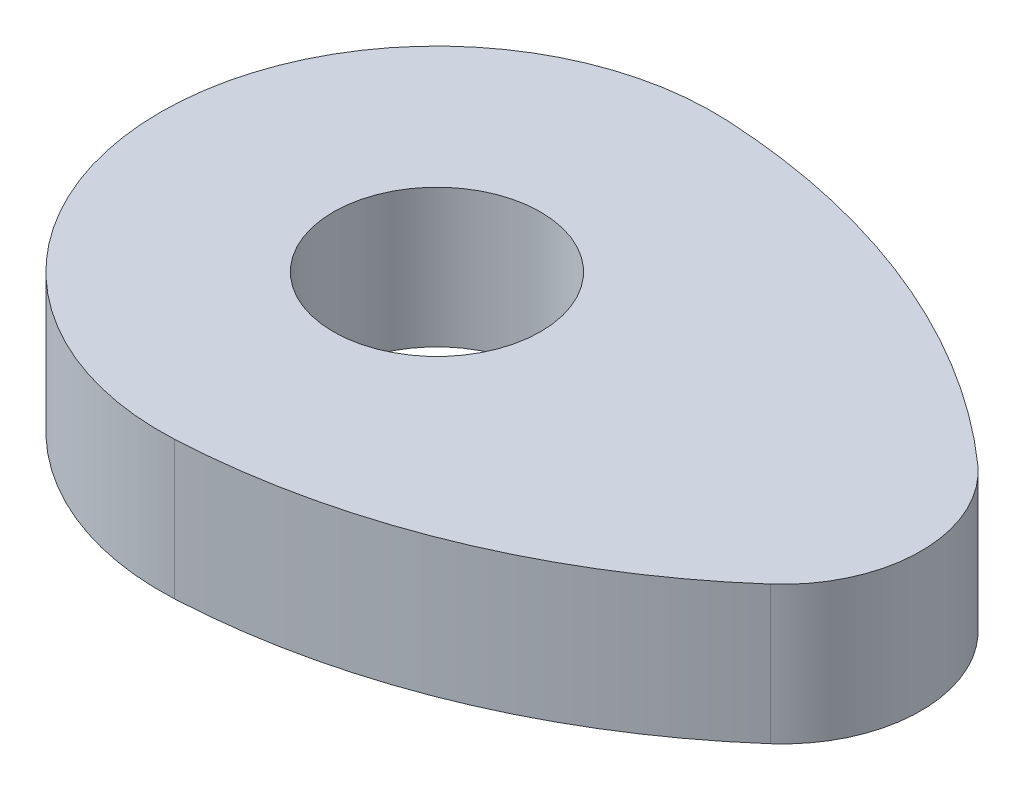
SolidWorks part; units mm, degrees
ref_plane "Front Plane" through (0, 0, 0) normal (0, 0, 1) x (1, 0, 0)
ref_plane "Top Plane" through (0, 0, 0) normal (0, 1, 0) x (1, 0, 0)
ref_plane "Right Plane" through (0, 0, 0) normal (1, 0, 0) x (0, 0, -1)
sketch "Sketch1" plane through (0, 0, 0) normal (0, 1, 0) x (1, 0, 0)
  arc A0 (1, 19.975) -> (1, -19.975) centre (0, 0) ccw
  arc A1 (31.625, -7.4906) -> (31.625, 7.4906) centre (25, 0) ccw
  arc A2 (1, 19.975) -> (31.625, 7.4906) centre (-1.5, -29.9625) cw
  arc A3 (1, -19.975) -> (31.625, -7.4906) centre (-1.5, 29.9625) ccw
  circle A4 centre (0, 0) radius 7.5
  dimension "D1" = 40
  dimension "D2" = 20
  dimension "D4" = 50
  dimension "D5" = 50
  dimension "D6" = 15
  dimension "D3" = 25
extrude "Boss-Extrude1" add sketch "Sketch1" along normal mid plane 10
ref_axis "Axis1" through (0, 5, 0) along (0, -1, 0)
